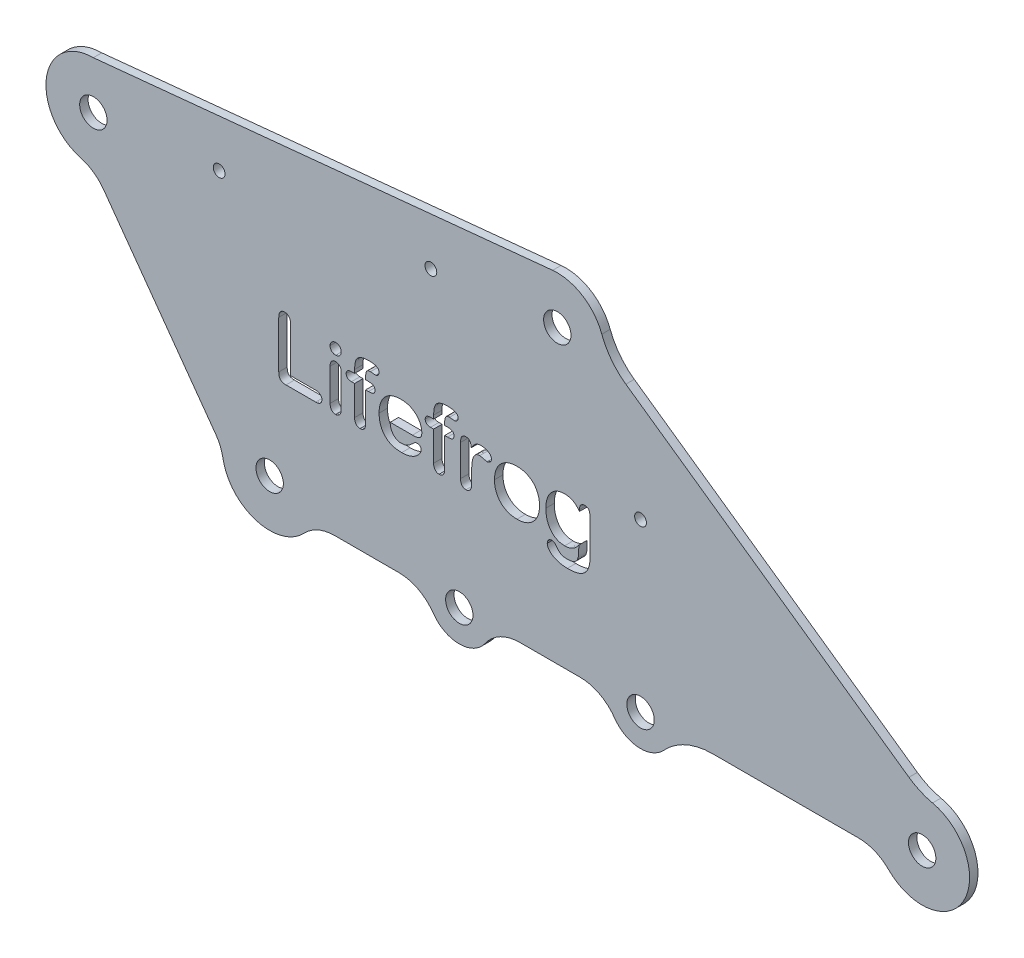
SolidWorks part; units mm, degrees
ref_plane "Front Plane" through (0, 0, 0) normal (0, 0, 1) x (1, 0, 0)
ref_plane "Top Plane" through (0, 0, 0) normal (0, 1, 0) x (1, 0, 0)
ref_plane "Right Plane" through (0, 0, 0) normal (1, 0, 0) x (0, 0, -1)
sketch "Sketch2" plane through (0, 0, 0) normal (0, 0, 1) x (1, 0, 0)
  line L0 (-96.303, -40.0195) -> (103.697, -40.0195) construction
  line L1 (56.1417, 22.4699) -> (-27.5885, 22.4699) construction
  line L2 (56.1417, 22.4699) -> (56.1417, -53.9544) construction
  line L3 (56.1417, -53.9544) -> (-159.2025, -53.9544) construction
  line L4 (-159.2025, 22.4699) -> (-159.2025, -53.9544) construction
  line L5 (-96.303, -40.0195) -> (-53.2713, -40.0195) construction
  line L6 (-100.4268, -47.0897) -> (-100.4268, -59.5897) construction
  line L7 (-100.4268, -59.5897) -> (73.7025, -59.5897) construction
  line L8 (-100.4268, -59.5897) -> (-302.9325, -59.5897) construction
  line L9 (-62.0853, -59.5897) -> (-73.2496, -62.9155) construction
  line L10 (-19.0853, -47.0897) -> (-15.8353, -47.0897) construction
  line L11 (47.7386, -47.0897) -> (47.7386, -41.2921) construction
  line L12 (-62.0853, -47.0897) -> (-107.0853, -47.0897) construction
  line L13 (-107.0853, -47.0897) -> (-107.0853, -42.5195) construction
  line L14 (-62.0853, -47.0897) -> (-58.8353, -47.0897) construction
  line L15 (-167.9726, 11.2199) -> (-124.5853, -42.5195) construction
  line L16 (-124.5853, -42.5195) -> (-167.9726, -37.8951) construction
  line L17 (-167.9726, -37.8951) -> (-167.9726, 11.2199) construction
  line L18 (-167.9726, -37.8951) -> (-167.9726, -59.5897) construction
  line L19 (-146.4823, -3.4151) -> (-119.9002, -40.3454)
  line L21 (-148.9187, 22.4699) -> (-39.9417, 33.2746)
  line L24 (-22.5647, 18.5545) -> (44.5996, -28.6343)
  line L25 (11.3122, -40.0195) -> (103.697, -40.0195) construction
  line L26 (-41.384, 22.4699) -> (-159.2025, 22.4699) construction
  line L27 (-47.7239, -47.0897) -> (-33.4467, -47.0897)
  line L28 (-1.9905, -47.0897) -> (32.6866, -47.0897)
  line L29 (-76.4467, -47.0897) -> (-91.6169, -47.0897)
  line L30 (-54.5853, -47.0897) -> (-19.0853, -47.0897) construction
  line L31 (-11.5853, -47.0897) -> (47.7386, -47.0897) construction
  line L32 (-148.9187, 11.2199) -> (-38.8318, 22.0795) construction
  arc A0 (-26.3612, 21.2219) -> (-51.3257, 22.4699) centre (-38.8318, 22.0795) ccw construction
  circle A1 centre (-38.8318, 22.0795) radius 3.25 construction
  arc A2 (-74.5853, -47.0897) -> (-51.639, -53.9544) centre (-62.0853, -47.0897) ccw construction
  circle A3 centre (-62.0853, -47.0897) radius 3.25 construction
  circle A4 centre (47.7386, -42.0897) radius 3.25
  circle A5 centre (-19.0853, -47.0897) radius 3.25 construction
  circle A6 centre (47.7386, -42.0897) radius 17.5 construction
  circle A7 centre (47.7386, -42.0897) radius 3.25 construction
  circle A8 centre (-107.0853, -42.5195) radius 17.5 construction
  circle A9 centre (-107.0853, -42.5195) radius 3.25 construction
  circle A10 centre (-148.9187, 11.2199) radius 19.0539 construction
  circle A11 centre (-148.9187, 11.2199) radius 3.25 construction
  arc A12 (-148.9187, 22.4699) -> (-151.9256, 0.3791) centre (-148.9187, 11.2199) ccw
  arc A13 (-118.1664, -44.4613) -> (-98.8961, -50.2332) centre (-107.0853, -42.5195) ccw
  arc A14 (-28.2784, 25.9769) -> (-39.9417, 33.2746) centre (-38.8318, 22.0795) ccw
  arc A15 (-68.2402, -51.3754) -> (-55.9304, -51.3754) centre (-62.0853, -47.0897) ccw
  arc A16 (-25.2402, -51.3754) -> (-13.5666, -52.1685) centre (-19.0853, -47.0897) ccw
  arc A17 (39.7699, -50.0309) -> (50.2007, -31.1125) centre (47.7386, -42.0897) ccw
  arc A18 (-7.7098, -42.5525) -> (-9.0853, -40.0195) centre (-19.0853, -47.0897) ccw construction
  arc A19 (-31.8119, -47.0897) -> (-8.3689, -53.9544) centre (-19.0853, -47.0897) ccw construction
  circle A20 centre (-19.0853, -47.0897) radius 3.25
  circle A21 centre (-62.0853, -47.0897) radius 3.25
  circle A22 centre (-107.0853, -42.5195) radius 3.25
  circle A23 centre (-148.9187, 11.2199) radius 3.25
  circle A24 centre (-38.8318, 22.0795) radius 3.25
  arc A25 (32.6866, -47.0897) -> (39.7699, -50.0309) centre (32.6866, -57.0897) cw
  arc A26 (-146.4823, -3.4151) -> (-151.9256, 0.3791) centre (-154.5984, -9.257) ccw
  arc A27 (-119.9002, -40.3454) -> (-118.1664, -44.4613) centre (-128.0164, -46.1873) cw
  arc A28 (-91.6169, -47.0897) -> (-98.8961, -50.2332) centre (-91.6169, -57.0897) ccw
  arc A29 (-76.4467, -47.0897) -> (-68.2402, -51.3754) centre (-76.4467, -57.0897) cw
  arc A30 (-33.4467, -47.0897) -> (-25.2402, -51.3754) centre (-33.4467, -57.0897) cw
  arc A31 (-47.7239, -47.0897) -> (-55.9304, -51.3754) centre (-47.7239, -57.0897) ccw
  arc A33 (-22.5647, 18.5545) -> (-28.2784, 25.9769) centre (-13.5206, 31.4271) cw
  arc A34 (44.5996, -28.6343) -> (50.2007, -31.1125) centre (53.6437, -15.7617) ccw
  arc A35 (-1.9905, -47.0897) -> (-13.5666, -52.1685) centre (-1.9905, -62.8218) ccw
  point P67 (37.6608, -47.0897)
  point P70 (-148.9187, -0.0301)
  point P73 (-118.3353, -42.5195)
  point P76 (-96.8054, -47.0897)
  point P79 (-69.5853, -47.0897)
  point P82 (-26.5853, -47.0897)
  point P91 (-27.5818, 22.0795)
  point P94 (47.7386, -30.8397)
  dimension "D1" = 25
  dimension "D2" = 6.5
  dimension "D5" = 35
  dimension "D6" = 6.5
  dimension "D10" = 22.5
  dimension "D11" = 22.5
  dimension "D12" = 22.5
  dimension "D13" = 6.5
  dimension "D14" = 6.5
  dimension "D15" = 15
  dimension "D16" = 15
  dimension "D17" = 22.5
  dimension "D18" = 10
  dimension "D3" = 20
  dimension "D4" = 0
  dimension "D7" = 45
  dimension "D8" = 43
  dimension "D9" = 45
extrude "Boss-Extrude1" add sketch "Sketch2" along normal blind 2
sketch "Sketch5" plane through (0, 0, 2) normal (0, 0, 1) x (1, 0, 0)
  line L1 (-106.4284, -21.9146) -> (-30.7738, -21.9146) construction
  line L2 (-106.4284, -21.9146) -> (-106.4284, -6.1743) construction
  line L3 (-106.4284, -6.1743) -> (-30.7738, -6.1743) construction
  line L4 (-30.7738, -21.9146) -> (-30.7738, -6.1743) construction
  text T0 "Lifefrog" font "Arial Rounded MT Bold" height 15
  point P5 (-106.4284, -21.2135)
sketch "Sketch7" plane through (0, 0, 2) normal (0, 0, 1) x (1, 0, 0)
  line L0 (-148.9187, 11.2199) -> (-38.8318, 22.0795) construction
  line L1 (-148.9187, 11.2199) -> (-107.0853, -42.5195) construction
  line L2 (-107.0853, -42.5195) -> (25.9147, -42.5195) construction
  line L3 (25.9147, -42.5195) -> (-38.8318, 22.0795) construction
  line L5 (-107.0853, -2.5195) -> (-35.0853, -2.5195) construction
  line L6 (25.9147, -42.5195) -> (25.9147, -7.5195) construction
  line L7 (25.9147, -7.5195) -> (-64.0853, -7.5195) construction
  circle A0 centre (-119.0636, 14.1649) radius 1.4
  circle A1 centre (-68.8318, 19.1201) radius 1.4
  circle A5 centre (-19.0853, -7.5195) radius 1.4
  dimension "D1" = 2.8
  dimension "D2" = 2.8
  dimension "D4" = 30
  dimension "D5" = 2.8
  dimension "D6" = 40
  dimension "D3" = 30
  dimension "D7" = 35
  dimension "D9" = 45
extrude "Cut-Extrude4" cut sketch "Sketch7" against normal through all
extrude "Cut-Extrude5" cut sketch "Sketch5" against normal blind 10
sketch "Sketch8" plane through (0, 0, 2) normal (0, 0, 1) x (1, 0, 0)
  line L0 (-77.3813, -14.5454) -> (-75.1653, -14.5454) construction
  line L1 (-77.3813, -12.2092) -> (-75.1653, -12.2092)
  line L2 (-77.3813, -16.8816) -> (-75.1653, -16.8816)
  arc A0 (-77.3813, -12.2092) -> (-77.3813, -16.8816) centre (-77.3813, -14.5454) ccw
  arc A1 (-75.1653, -16.8816) -> (-75.1653, -12.2092) centre (-75.1653, -14.5454) ccw
  circle A2 centre (-48.7434, -16.6446) radius 4.4437
  circle A3 centre (-36.9422, -16.6446) radius 3.9871
  point P2 (-76.2733, -14.5454)
extrude "Cut-Extrude6" cut sketch "Sketch8" against normal blind 10
